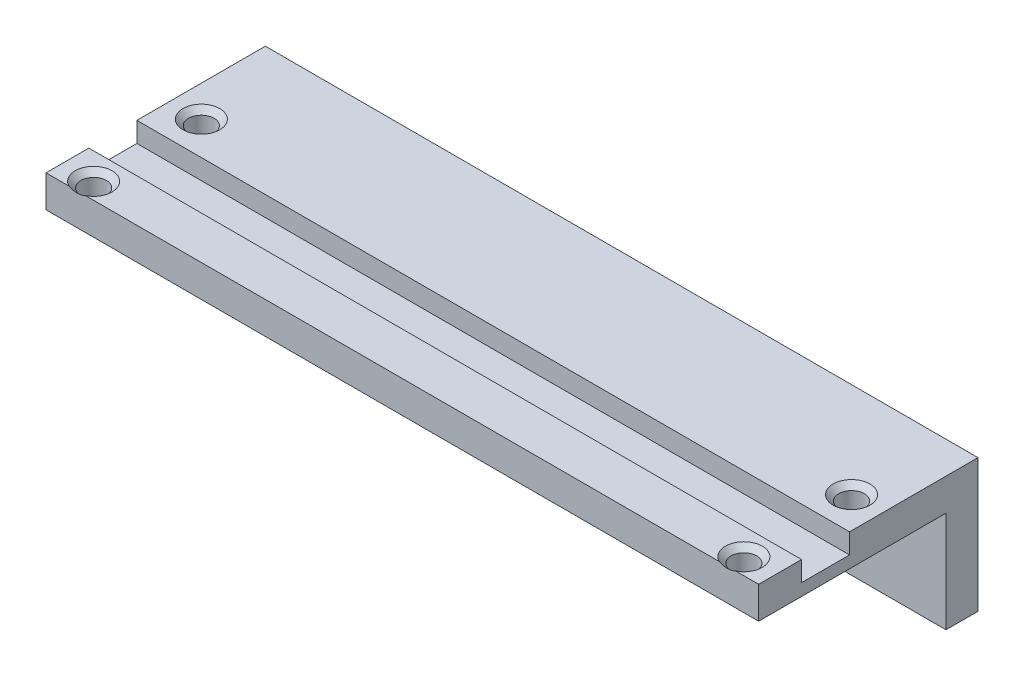
SolidWorks part; units mm, degrees
ref_plane "Front Plane" through (0, 0, 0) normal (0, 0, 1) x (1, 0, 0)
ref_plane "Top Plane" through (0, 0, 0) normal (0, 1, 0) x (1, 0, 0)
ref_plane "Right Plane" through (0, 0, 0) normal (1, 0, 0) x (0, 0, -1)
sketch "Sketch1" plane through (0, 0, 0) normal (0, 1, 0) x (1, 0, 0)
  line L5 (-44.5, 12) -> (44.5, 12)
  line L6 (-44.5, 12) -> (-44.5, -12)
  line L7 (-44.5, -12) -> (44.5, -12)
  line L8 (44.5, 12) -> (44.5, -12)
  line L9 (-44.5, 12) -> (44.5, -12) construction
  line L10 (-44.5, -12) -> (44.5, 12) construction
  point P0 (0, 0)
  dimension "D1" = 89
  dimension "D2" = 24
extrude "Boss-Extrude1" add sketch "Sketch1" along normal blind 4
sketch "Sketch2" plane through (0, 4, 0) normal (0, 1, 0) x (1, 0, 0)
  circle A0 centre (-40.6, 3.5) radius 1.6
  circle A2 centre (-40.6, -9.95) radius 1.6
  circle A3 centre (40.6, 3.5) radius 1.6
  circle A4 centre (40.6, -9.95) radius 1.6
  line B0 (-42.6, 12) -> (-42.6, -12)
  line B1 (-42.6, -12) -> (42.6, -12)
  line B2 (42.6, -12) -> (42.6, 12)
  line B3 (42.6, 12) -> (-42.6, 12)
  line B4 (-42.6, 0) -> (42.6, 0) construction
  line B5 (0, 12) -> (0, -12) construction
  arc B6 (41.75, -9.95) -> (39.45, -9.95) centre (40.6, -9.95) ccw
  arc B7 (39.45, -9.95) -> (41.75, -9.95) centre (40.6, -9.95) ccw
  arc B8 (41.75, 3.5) -> (39.45, 3.5) centre (40.6, 3.5) ccw
  arc B9 (39.45, 3.5) -> (41.75, 3.5) centre (40.6, 3.5) ccw
  arc B10 (11.65, 3.5) -> (9.35, 3.5) centre (10.5, 3.5) ccw
  arc B11 (9.35, 3.5) -> (11.65, 3.5) centre (10.5, 3.5) ccw
  arc B12 (11.65, -9.95) -> (9.35, -9.95) centre (10.5, -9.95) ccw
  arc B13 (9.35, -9.95) -> (11.65, -9.95) centre (10.5, -9.95) ccw
  arc B14 (-39.45, -9.95) -> (-41.75, -9.95) centre (-40.6, -9.95) ccw
  arc B15 (-41.75, -9.95) -> (-39.45, -9.95) centre (-40.6, -9.95) ccw
  arc B16 (-39.45, 3.5) -> (-41.75, 3.5) centre (-40.6, 3.5) ccw
  arc B17 (-41.75, 3.5) -> (-39.45, 3.5) centre (-40.6, 3.5) ccw
  arc B18 (-22.05, -3.65) -> (-20.55, -3.65) centre (-21.3, -3.65) ccw
  arc B19 (-20.55, -3.65) -> (-22.05, -3.65) centre (-21.3, -3.65) ccw
  arc B20 (-9.35, -9.95) -> (-11.65, -9.95) centre (-10.5, -9.95) ccw
  arc B21 (-11.65, -9.95) -> (-9.35, -9.95) centre (-10.5, -9.95) ccw
  arc B22 (20.55, -3.65) -> (22.05, -3.65) centre (21.3, -3.65) ccw
  arc B23 (22.05, -3.65) -> (20.55, -3.65) centre (21.3, -3.65) ccw
  arc B24 (-39.55, -3.65) -> (-38.05, -3.65) centre (-38.8, -3.65) ccw
  arc B25 (-38.05, -3.65) -> (-39.55, -3.65) centre (-38.8, -3.65) ccw
  arc B26 (38.05, -3.65) -> (39.55, -3.65) centre (38.8, -3.65) ccw
  arc B27 (39.55, -3.65) -> (38.05, -3.65) centre (38.8, -3.65) ccw
  arc B28 (-11.65, 3.5) -> (-9.35, 3.5) centre (-10.5, 3.5) ccw
  arc B29 (-9.35, 3.5) -> (-11.65, 3.5) centre (-10.5, 3.5) ccw
  dimension "D1" = 3.2
  dimension "D2" = 3.2
  dimension "D3" = 3.2
  dimension "D4" = 3.2
sketch_block_instance "Block2-2"
sketch_block "Block2"
extrude "Cut-Extrude1" cut sketch "Sketch2" against normal through all contours A2 | A4 | A0 | A3
chamfer "Chamfer1" distance 0.7 angle 45 4 edges at (-40.6, 4, 11.55) (-40.6, 4, -1.9) (40.6, 4, -1.9) (40.6, 4, 11.55)
sketch "Sketch3" plane through (0, 4, 0) normal (0, 1, 0) x (1, 0, 0)
  line L0 (-44.5, 12) -> (-44.5, -12) construction
  line L1 (-44.5, -0.65) -> (44.5, -0.65)
  line L2 (-44.5, -0.65) -> (-44.5, -6.65)
  line L3 (-44.5, -6.65) -> (44.5, -6.65)
  line L4 (44.5, -0.65) -> (44.5, -6.65)
  line L5 (44.5, -12) -> (44.5, 12) construction
  line L6 (-44.5, -3.65) -> (44.5, -3.65) construction
  line L7 (-38.8, -3.65) -> (-21.3, -3.65) construction
  line B0 (-42.6, 12) -> (-42.6, -12)
  line B1 (-42.6, -12) -> (42.6, -12)
  line B2 (42.6, -12) -> (42.6, 12)
  line B3 (42.6, 12) -> (-42.6, 12)
  line B4 (-42.6, 0) -> (42.6, 0) construction
  line B5 (0, 12) -> (0, -12) construction
  arc B6 (41.75, -9.95) -> (39.45, -9.95) centre (40.6, -9.95) ccw
  arc B7 (39.45, -9.95) -> (41.75, -9.95) centre (40.6, -9.95) ccw
  arc B8 (41.75, 3.5) -> (39.45, 3.5) centre (40.6, 3.5) ccw
  arc B9 (39.45, 3.5) -> (41.75, 3.5) centre (40.6, 3.5) ccw
  arc B10 (11.65, 3.5) -> (9.35, 3.5) centre (10.5, 3.5) ccw
  arc B11 (9.35, 3.5) -> (11.65, 3.5) centre (10.5, 3.5) ccw
  arc B12 (11.65, -9.95) -> (9.35, -9.95) centre (10.5, -9.95) ccw
  arc B13 (9.35, -9.95) -> (11.65, -9.95) centre (10.5, -9.95) ccw
  arc B14 (-39.45, -9.95) -> (-41.75, -9.95) centre (-40.6, -9.95) ccw
  arc B15 (-41.75, -9.95) -> (-39.45, -9.95) centre (-40.6, -9.95) ccw
  arc B16 (-39.45, 3.5) -> (-41.75, 3.5) centre (-40.6, 3.5) ccw
  arc B17 (-41.75, 3.5) -> (-39.45, 3.5) centre (-40.6, 3.5) ccw
  arc B18 (-22.05, -3.65) -> (-20.55, -3.65) centre (-21.3, -3.65) ccw
  arc B19 (-20.55, -3.65) -> (-22.05, -3.65) centre (-21.3, -3.65) ccw
  arc B20 (-9.35, -9.95) -> (-11.65, -9.95) centre (-10.5, -9.95) ccw
  arc B21 (-11.65, -9.95) -> (-9.35, -9.95) centre (-10.5, -9.95) ccw
  arc B22 (20.55, -3.65) -> (22.05, -3.65) centre (21.3, -3.65) ccw
  arc B23 (22.05, -3.65) -> (20.55, -3.65) centre (21.3, -3.65) ccw
  arc B24 (-39.55, -3.65) -> (-38.05, -3.65) centre (-38.8, -3.65) ccw
  arc B25 (-38.05, -3.65) -> (-39.55, -3.65) centre (-38.8, -3.65) ccw
  arc B26 (38.05, -3.65) -> (39.55, -3.65) centre (38.8, -3.65) ccw
  arc B27 (39.55, -3.65) -> (38.05, -3.65) centre (38.8, -3.65) ccw
  arc B28 (-11.65, 3.5) -> (-9.35, 3.5) centre (-10.5, 3.5) ccw
  arc B29 (-9.35, 3.5) -> (-11.65, 3.5) centre (-10.5, 3.5) ccw
  dimension "D1" = 6
sketch_block_instance "Block2-3"
extrude "Cut-Extrude2" cut sketch "Sketch3" against normal blind 2.5 contours L2 L1 L4 L3
sketch "Sketch4" plane through (0, 0, -12) normal (0, 0, -1) x (-1, 0, 0)
  line L1 (-44.5, 4) -> (44.5, 4)
  line L2 (-44.5, 4) -> (-44.5, 0)
  line L3 (-44.5, 0) -> (44.5, 0)
  line L4 (44.5, 4) -> (44.5, 0)
extrude "Boss-Extrude2" add sketch "Sketch4" along normal blind 3.39
sketch "Sketch5" plane through (0, 0, 0) normal (0, -1, 0) x (1, 0, 0)
  line L0 (44.5, 12) -> (44.5, -15.39) construction
  line L1 (-44.5, -15.39) -> (44.5, -15.39)
  line L2 (-44.5, -15.39) -> (-44.5, -11.39)
  line L3 (-44.5, -11.39) -> (44.5, -11.39)
  line L4 (44.5, -15.39) -> (44.5, -11.39)
  dimension "D1" = 4
extrude "Boss-Extrude3" add sketch "Sketch5" along normal blind 12.62
